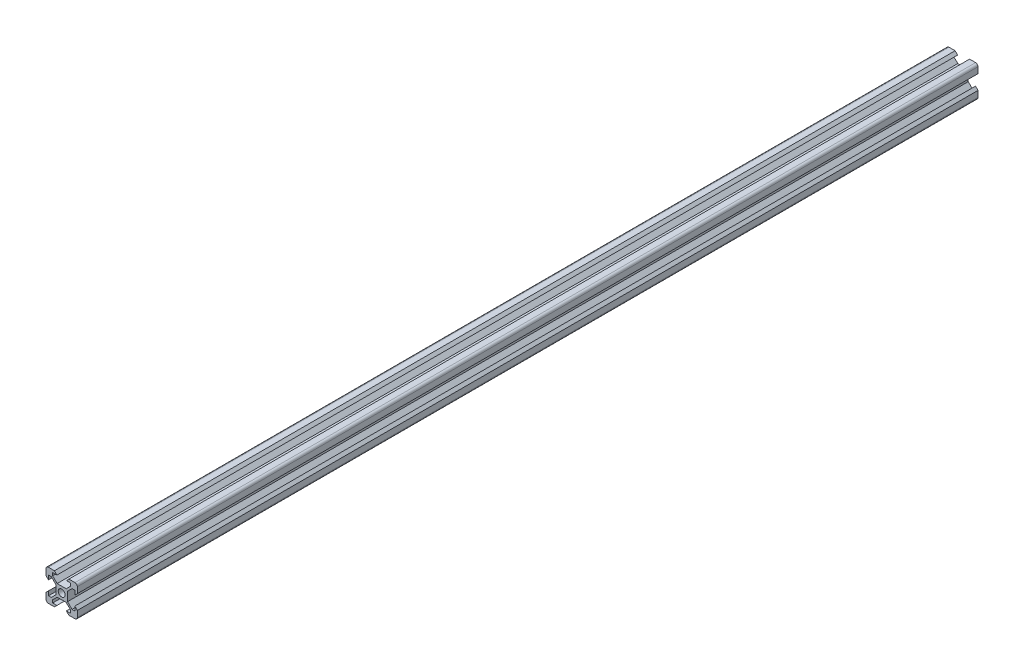
SolidWorks part; units mm, degrees
ref_plane "Front Plane" through (0, 0, 0) normal (0, 0, 1) x (1, 0, 0)
ref_plane "Top Plane" through (0, 0, 0) normal (0, 1, 0) x (1, 0, 0)
ref_plane "Right Plane" through (0, 0, 0) normal (1, 0, 0) x (0, 0, -1)
sketch "Sketch1" plane through (0, 0, 0) normal (0, 0, 1) x (1, 0, 0)
  line L0 (-5.7847, 7.544) -> (-11.512, 13.2713)
  line L1 (-7.544, 7.544) -> (7.544, 7.544)
  line L2 (-7.544, 7.544) -> (-7.544, -7.544)
  line L3 (-7.544, -7.544) -> (7.544, -7.544)
  line L4 (7.544, 7.544) -> (7.544, -7.544)
  line L5 (-7.544, 7.544) -> (7.544, -7.544) construction
  line L6 (-7.544, -7.544) -> (7.544, 7.544) construction
  line L7 (-11.512, 13.2713) -> (-11.512, 16.8)
  line L8 (-11.512, 16.8) -> (-6.052, 16.8)
  line L9 (-6.052, 16.8) -> (-9.252, 20)
  line L10 (-9.252, 20) -> (-17, 20)
  line L11 (-20, 17) -> (-20, 9.252)
  line L12 (-20, 9.252) -> (-16.8, 6.052)
  line L13 (-16.8, 6.052) -> (-16.8, 11.512)
  line L14 (-16.8, 11.512) -> (-13.2713, 11.512)
  line L15 (-13.2713, 11.512) -> (-7.544, 5.7847)
  line L16 (-19.1213, 19.1213) -> (0, 0) construction
  line L17 (13.2713, 11.512) -> (16.8, 11.512)
  line L18 (20, 9.252) -> (20, 17)
  line L19 (17, 20) -> (9.252, 20)
  line L20 (9.252, 20) -> (6.052, 16.8)
  line L21 (6.052, 16.8) -> (11.512, 16.8)
  line L22 (11.512, 16.8) -> (11.512, 13.2713)
  line L23 (11.512, 13.2713) -> (5.7847, 7.544)
  line L24 (7.544, 5.7847) -> (13.2713, 11.512)
  line L25 (16.8, 11.512) -> (16.8, 6.052)
  line L26 (16.8, 6.052) -> (20, 9.252)
  line L27 (19.1213, 19.1213) -> (0, 0) construction
  line L28 (11.512, -13.2713) -> (11.512, -16.8)
  line L29 (9.252, -20) -> (17, -20)
  line L30 (20, -17) -> (20, -9.252)
  line L31 (20, -9.252) -> (16.8, -6.052)
  line L32 (16.8, -6.052) -> (16.8, -11.512)
  line L33 (16.8, -11.512) -> (13.2713, -11.512)
  line L34 (13.2713, -11.512) -> (7.544, -5.7847)
  line L35 (5.7847, -7.544) -> (11.512, -13.2713)
  line L36 (11.512, -16.8) -> (6.052, -16.8)
  line L37 (6.052, -16.8) -> (9.252, -20)
  line L38 (19.1213, -19.1213) -> (0, 0) construction
  line L39 (-13.2713, -11.512) -> (-16.8, -11.512)
  line L40 (-20, -9.252) -> (-20, -17)
  line L41 (-17, -20) -> (-9.252, -20)
  line L42 (-9.252, -20) -> (-6.052, -16.8)
  line L43 (-6.052, -16.8) -> (-11.512, -16.8)
  line L44 (-11.512, -16.8) -> (-11.512, -13.2713)
  line L45 (-11.512, -13.2713) -> (-5.7847, -7.544)
  line L46 (-7.544, -5.7847) -> (-13.2713, -11.512)
  line L47 (-16.8, -11.512) -> (-16.8, -6.052)
  line L48 (-16.8, -6.052) -> (-20, -9.252)
  line L49 (-19.1213, -19.1213) -> (0, 0) construction
  circle A0 centre (0, 0) radius 4.4
  arc A1 (-17, 20) -> (-20, 17) centre (-17, 17) ccw
  arc A2 (20, 17) -> (17, 20) centre (17, 17) ccw
  arc A3 (17, -20) -> (20, -17) centre (17, -17) ccw
  arc A4 (-20, -17) -> (-17, -20) centre (-17, -17) ccw
  point P66 (0, 0)
  dimension "D1" = 8.8
  dimension "D8" = 3
  dimension "D2" = 15.088
  dimension "D3" = 2.488
  dimension "D4" = 8.488
  dimension "D5" = 3.2
  dimension "D6" = 20
  dimension "D7" = 15.2
  dimension "D9" = 4
extrude "Boss-Extrude1" add sketch "Sketch1" along normal mid plane 1150 contours L10 A1 L11 L12 L13 L14 L15 L2 L1 L0 L7 L8 L9 | L18 A2 L19 L20 L21 L22 L23 L1 L4 L24 L17 L25 L26 | L40 A4 L41 L42 L43 L44 L45 L3 L2 L46 L39 L47 L48 | L29 A3 L30 L31 L32 L33 L34 L4 L3 L35 L28 L36 L37 | L4 L1 L2 L3 A0 region at (-14.3184, 14.3184, 0) region at (0, 7.3306, 0) region at (14.3184, 14.3184, 0) region at (-14.3184, -14.3184, 0) region at (14.3184, -14.3184, 0)
equation "\"longitud\"= 800"
